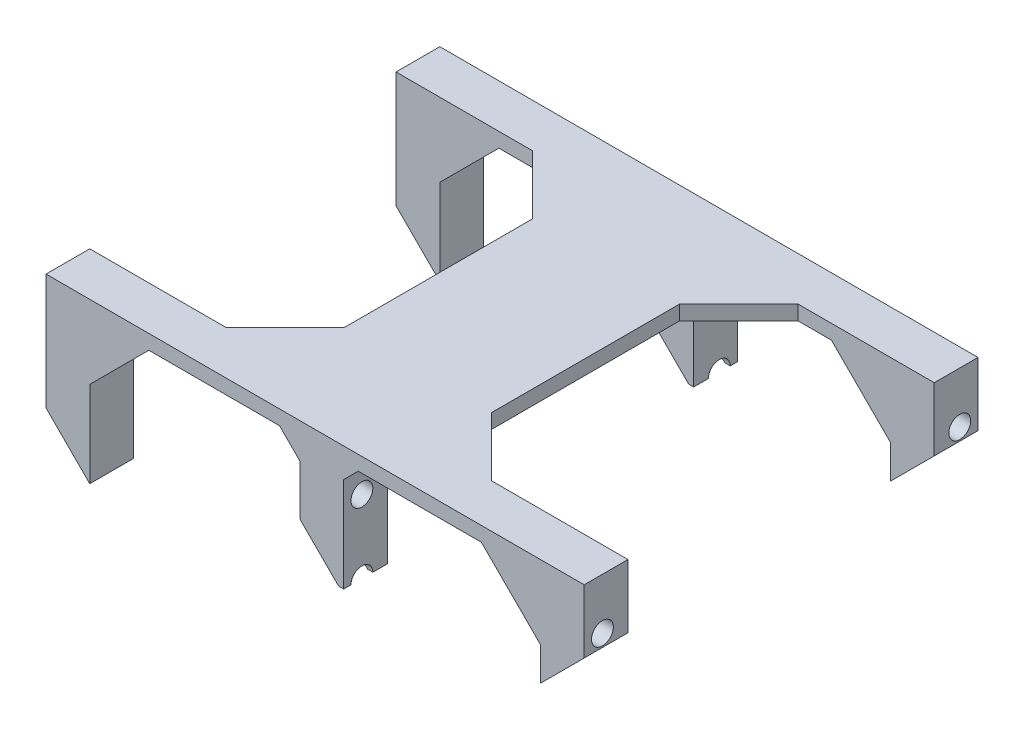
SolidWorks part; units mm, degrees
ref_plane "Front Plane" through (0, 0, 0) normal (0, 0, 1) x (1, 0, 0)
ref_plane "Top Plane" through (0, 0, 0) normal (0, 1, 0) x (1, 0, 0)
ref_plane "Right Plane" through (0, 0, 0) normal (1, 0, 0) x (0, 0, -1)
sketch "Sketch1" plane through (0, 0, 0) normal (0, 1, 0) x (1, 0, 0)
  line L1 (-23.5, -27) -> (23.5, -27)
  line L2 (-23.5, -27) -> (-23.5, 27)
  line L3 (-23.5, 27) -> (23.5, 27)
  line L4 (23.5, -27) -> (23.5, 27)
  line L5 (-23.5, -27) -> (23.5, 27) construction
  line L6 (-23.5, 27) -> (23.5, -27) construction
  point P0 (0, 0)
  dimension "D1" = 54
  dimension "D2" = 47
extrude "Boss-Extrude1" add sketch "Sketch1" along normal blind 2
sketch "Sketch2" plane through (0, 0, 0) normal (0, -1, 0) x (1, 0, 0)
  line L0 (0, 0) -> (-23.5, 0) construction
  line L5 (-23.5, 27) -> (23.5, 27) construction
  line L6 (-15.48, 27) -> (-9.48, 27)
  line L7 (-23.5, -27) -> (-23.5, 27) construction
  line L8 (-15.48, 27) -> (-15.48, 21)
  line L9 (23.5, 27) -> (17.5, 27)
  line L10 (23.5, 27) -> (23.5, 21)
  line L11 (23.5, 21) -> (17.5, 21)
  line L12 (17.5, 27) -> (17.5, 21)
  line L13 (23.5, 27) -> (17.5, 21) construction
  line L14 (23.5, 21) -> (17.5, 27) construction
  line L15 (23.5, -27) -> (17.5, -27)
  line L16 (23.5, -27) -> (23.5, -21)
  line L17 (23.5, -21) -> (17.5, -21)
  line L18 (17.5, -27) -> (17.5, -21)
  line L19 (23.5, -27) -> (17.5, -21) construction
  line L20 (23.5, -21) -> (17.5, -27) construction
  line L21 (-15.48, 21) -> (-9.48, 21)
  line L22 (-9.48, 27) -> (-9.48, 21)
  line L23 (-15.48, 27) -> (-9.48, 21) construction
  line L24 (-15.48, 21) -> (-9.48, 27) construction
  line L25 (-15.48, -21) -> (-9.48, -27) construction
  line L26 (-15.48, -27) -> (-9.48, -21) construction
  line L27 (-9.48, -27) -> (-9.48, -21)
  line L28 (-15.48, -21) -> (-9.48, -21)
  line L29 (-15.48, -27) -> (-15.48, -21)
  line L30 (-15.48, -27) -> (-9.48, -27)
  point P4 (-12.48, 24)
  point P15 (20.5, 24)
  point P21 (20.5, -24)
  point P29 (-12.48, -24)
  dimension "D1" = 6
  dimension "D2" = 6
  dimension "D3" = 6
  dimension "D4" = 6
  dimension "D5" = 6
  dimension "D6" = 6
  dimension "D7" = 8.02
extrude "Boss-Extrude2" add sketch "Sketch2" along normal blind 15
chamfer "Chamfer1" distance 5.3 angle 45 2 edges at (-15.48, -15, 24) (-15.48, -15, -24)
chamfer "Chamfer2" distance 8.3 angle 45 2 edges at (23.5, -15, -24) (23.5, -15, 24)
sketch "Sketch3" plane through (-15.48, 0, 0) normal (-1, 0, 0) x (0, 0, 1)
  circle A0 centre (24.5, -5) radius 1.5
  circle A1 centre (-24.5, -5) radius 1.5
  circle A2 centre (24.5, -15) radius 1.5
  circle A3 centre (-24.5, -15) radius 1.5
  dimension "D1" = 3
  dimension "D2" = 3
  dimension "D3" = 3
  dimension "D4" = 3
extrude "Cut-Extrude1" cut sketch "Sketch3" against normal through all
chamfer "Chamfer3" distance 2.8 angle 45 2 edges at (-15.48, 0, 24) (-15.48, 0, -24)
chamfer "Chamfer4" distance 2 angle 45 2 edges at (-9.48, 0, 24) (-9.48, 0, -24)
sketch "Sketch4" plane through (-23.5, 0, 0) normal (-1, 0, 0) x (0, 0, 1)
  line L1 (27, 2) -> (21, 2)
  line L2 (27, 2) -> (27, 0)
  line L3 (27, 0) -> (21, 0)
  line L4 (21, 2) -> (21, 0)
  line L5 (27, 2) -> (21, 0) construction
  line L6 (27, 0) -> (21, 2) construction
  line L7 (-27, 2) -> (-21, 2)
  line L8 (-27, 2) -> (-27, 0)
  line L9 (-27, 0) -> (-21, 0)
  line L10 (-21, 2) -> (-21, 0)
  line L11 (-27, 2) -> (-21, 0) construction
  line L12 (-27, 0) -> (-21, 2) construction
  point P4 (24, 1)
  point P11 (-24, 1)
extrude "Boss-Extrude3" add sketch "Sketch4" along normal blind 26.8
sketch "Sketch6" plane through (0, 0, 0) normal (0, -1, 0) x (1, 0, 0)
  line L0 (-50.3, 21) -> (-23.5, 21) construction
  line L1 (-50.3, 27) -> (-44.3, 27)
  line L2 (-50.3, 27) -> (-50.3, 21)
  line L3 (-50.3, 21) -> (-44.3, 21)
  line L4 (-44.3, 27) -> (-44.3, 21)
  line L5 (-50.3, 27) -> (-44.3, 21) construction
  line L6 (-50.3, 21) -> (-44.3, 27) construction
  line L7 (-50.3, -21) -> (-23.5, -21) construction
  line L8 (-50.3, -27) -> (-44.3, -27)
  line L9 (-50.3, -27) -> (-50.3, -21)
  line L10 (-50.3, -21) -> (-44.3, -21)
  line L11 (-44.3, -27) -> (-44.3, -21)
  line L12 (-50.3, -27) -> (-44.3, -21) construction
  line L13 (-50.3, -21) -> (-44.3, -27) construction
  point P4 (-47.3, 24)
  point P12 (-47.3, -24)
  dimension "D1" = 6
extrude "Boss-Extrude4" add sketch "Sketch6" along normal blind 22
chamfer "Chamfer5" distance 8.1 angle 45 6 edges at (-44.3, 0, 24) (-44.3, 0, -24) (-23.5, 1, -21) (-23.5, 1, 21) (-50.3, -22, 24) (-50.3, -22, -24)
sketch "Sketch7" plane through (0, 0, 0) normal (0, -1, 0) x (1, 0, 0)
  line L0 (-36.2, 21) -> (-31.6, 21) construction
  line L1 (-36.2, 21) -> (-44.3, 21) construction
  line L2 (-44.3, 21) -> (-50.3, 21) construction
  line L3 (-50.3, -21) -> (-44.3, -21) construction
  line L4 (-36.2, -21) -> (-31.6, -21) construction
  line L5 (-44.3, -21) -> (-36.2, -21) construction
  line L6 (-23.5, -12.9) -> (-31.6, -21) construction
  line L7 (-23.5, -12.9) -> (-23.5, 12.9) construction
  line L8 (-31.6, 21) -> (-23.5, 12.9) construction
  line L9 (-36.2, 21) -> (-31.6, 21)
  line L10 (-36.2, 21) -> (-44.3, 21)
  line L11 (-44.3, 21) -> (-50.3, 21)
  line L12 (-50.3, -21) -> (-44.3, -21)
  line L13 (-36.2, -21) -> (-31.6, -21)
  line L14 (-44.3, -21) -> (-36.2, -21)
  line L15 (-23.5, -12.9) -> (-31.6, -21)
  line L16 (-23.5, -12.9) -> (-23.5, 12.9)
  line L17 (-31.6, 21) -> (-23.5, 12.9)
  line L18 (-50.3, 27) -> (23.5, 27)
  line L19 (-13.4, 27) -> (-13.4, -33) construction
  line L20 (4.8, 21) -> (-3.3, 12.9)
  line L21 (-3.3, -12.9) -> (-3.3, 12.9)
  line L22 (-3.3, -12.9) -> (4.8, -21)
  line L23 (17.5, -21) -> (9.4, -21)
  line L24 (9.4, -21) -> (4.8, -21)
  line L25 (23.5, -21) -> (17.5, -21)
  line L26 (17.5, 21) -> (23.5, 21)
  line L27 (9.4, 21) -> (17.5, 21)
  line L28 (9.4, 21) -> (4.8, 21)
  line L29 (23.5, 21) -> (23.5, -21)
  line M27 (17.5, -21) -> (23.5, -21)
  line M28 (23.5, -21) -> (23.5, 21)
  line M29 (23.5, 21) -> (17.5, 21)
  dimension "D1" = 60
extrude "Cut-Extrude2" cut sketch "Sketch7" against normal through all contours L27 L28 L20 L21 L22 L24 L23 M27 M28 M29 region at (10.7623, 0, 0)
chamfer "Chamfer6" distance 8.1 angle 45 2 edges at (17.5, 0, -24) (17.5, 0, 24)
sketch "Sketch8" plane through (-9.48, 0, 0) normal (1, 0, 0) x (0, 0, -1)
  circle A0 centre (-24.5, -5) radius 1.5 construction
  circle A1 centre (-24.5, -5) radius 1.5
  circle A2 centre (24.5, -5) radius 1.5 construction
  circle A3 centre (24.5, -5) radius 1.5
extrude "Cut-Extrude3" cut sketch "Sketch8" against normal through all both and the other way through all
